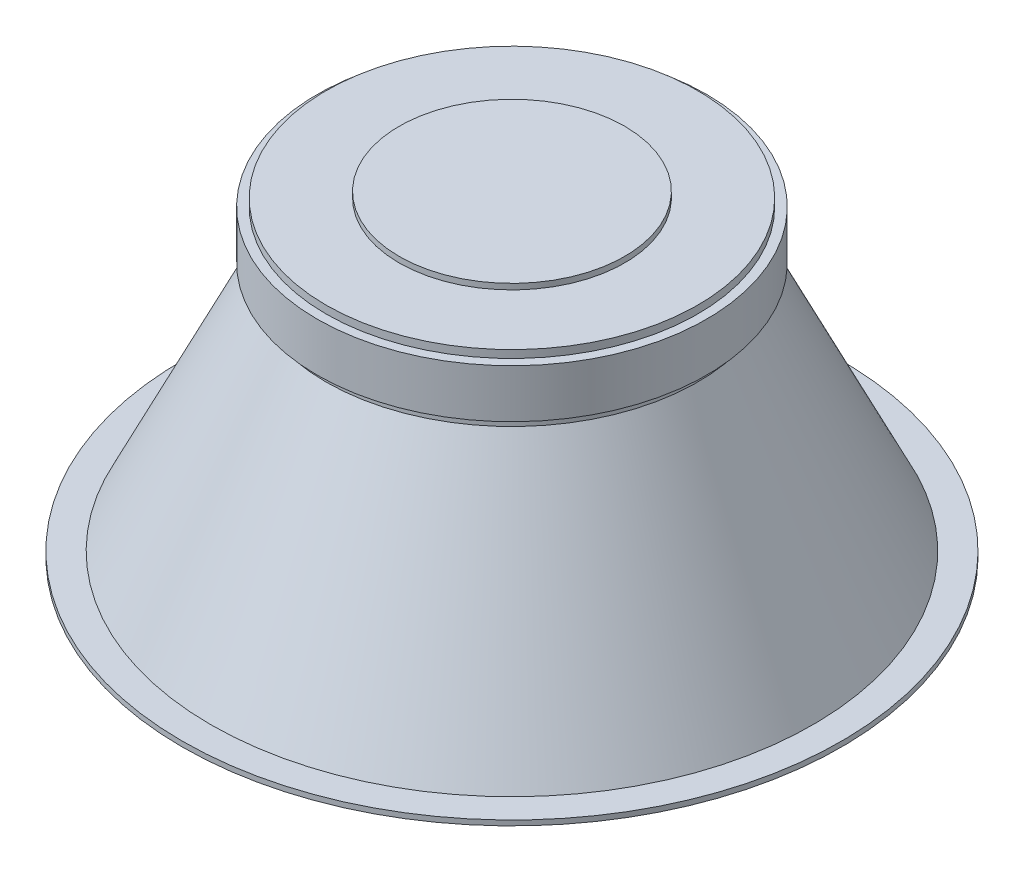
SolidWorks part; units mm, degrees
ref_plane "Front Plane" through (0, 0, 0) normal (0, 0, 1) x (1, 0, 0)
ref_plane "Top Plane" through (0, 0, 0) normal (0, 1, 0) x (1, 0, 0)
ref_plane "Right Plane" through (0, 0, 0) normal (1, 0, 0) x (0, 0, -1)
sketch "Sketch7" plane through (0, 0, 0) normal (1, 0, 0) x (0, 0, -1)
  line L0 (12.5742, 123.5) -> (-31.4258, 123.5)
  line L1 (-59.9258, 118.2794) -> (-63.3928, 118.2794)
  line L2 (-59.9258, 121.2831) -> (-59.9258, 118.2794)
  line L3 (-59.9258, 95.2831) -> (-104.9008, 2)
  line L4 (-104.9008, 2) -> (-116.0133, 2)
  line L5 (-59.9258, 99.3602) -> (-59.9258, 95.2831)
  line L6 (-116.0133, 2) -> (-116.0133, 0)
  line L7 (-116.0133, 0) -> (-102.3133, 0)
  line L8 (-63.3928, 99.3602) -> (-59.9258, 99.3602)
  line L9 (-102.3133, 0) -> (-102.3133, 2)
  line L25 (-91.7411, 3.4622) -> (-32.3943, 54.1395)
  line L26 (12.5742, 123.5) -> (12.5742, -9.999) construction
  line L27 (12.5742, 123.5) -> (12.5742, 39.6936)
  line L28 (-63.3928, 118.2794) -> (-63.3928, 99.3602)
  line L29 (-102.3133, 2) -> (-100.8367, 3.4622)
  line L30 (-96.2496, 2) -> (-94.773, 3.4622)
  line L31 (-93.2177, 2) -> (-91.7411, 3.4622)
  line L32 (-99.2815, 2) -> (-97.8048, 3.4622)
  line L33 (-100.8367, 3.4622) -> (-99.2815, 2)
  line L34 (-97.8048, 3.4622) -> (-96.2496, 2)
  line L35 (-94.773, 3.4622) -> (-93.2177, 2)
  line L36 (-31.4258, 123.5) -> (-31.4258, 121.2831)
  line L37 (-31.4258, 121.2831) -> (-59.9258, 121.2831)
  arc A0 (-32.3943, 54.1395) -> (12.5742, 39.6936) centre (12.5652, 116.8796) ccw
  point P2 (-116.0133, 1)
  point P3 (-77.5171, -3.2704)
  point P22 (0, 0)
  point P23 (0, 0)
  point P24 (0, 0)
  point P25 (0, 0)
  point P26 (-91.412, 3.6055)
  point P27 (0, 0)
  point P28 (0, 0)
  point P29 (0, 0)
  point P30 (0, 0)
  point P31 (10.3633, 139.7853)
  point P32 (0, 0)
  point P33 (10.3633, 139.7853)
  point P36 (0, 0)
  point P38 (10.3633, 139.7853)
  point P39 (0, 0)
  point P40 (0, 0)
  point P41 (0, 0)
  point P42 (0, 0)
  point P43 (0, 0)
  point P44 (-32.2085, 54.1395)
  point P45 (0, 0)
  point P46 (0, 0)
  point P47 (0, 0)
  point P48 (12.76, 39.6936)
  point P49 (-73.8282, 180.2422)
  point P52 (0, 0)
  point P53 (0, 0)
  point P54 (0, 0)
  point P55 (0, 0)
  point P56 (0, 0)
  point P57 (0, 0)
  point P58 (0, 0)
  point P59 (0, 0)
  point P60 (0, 0)
  point P61 (0, 0)
  point P62 (-31.24, 124.9533)
  dimension "D1" = 128.5875
  dimension "D2" = 117.475
  dimension "D3" = 13.7
  dimension "D5" = 26
  dimension "D6" = 44
  dimension "D7" = 123.5
  dimension "D4" = 72.5
revolve "Revolve1" add sketch "Sketch7" angle 360 about L26
equation "\"LENGTH\" = 1000mm"
equation "\"WIDTH\" = 300mm"
equation "\"HEIGHT\" = 300mm"
equation "\"HOUSING_DEPTH\" = 4mm"
equation "\"PLY\"= 12mm"
equation "\"CENTER_BRACE_LENGTH\" = 393mm"
equation "\"PANEL_WIDTH\"= \"LENGTH\" - \"CENTER_BRACE_LENGTH\" * 2 - \"PLY\" * 4"
equation "\"PANEL_SMALL_HEIGHT\" = 70mm"
equation "\"PORT_WIDTH\" = 90mm"
equation "\"PORT_RADIUS\" = 15mm"
equation "\"PORT_BRACE_HEIGHT\" = 92mm"
equation "\"DOWEL_SIZE\" = 0.25in"
equation "\"DOWEL_OFFSET\" = 30mm"
equation "\"GW1058_outside_diameter\" = 10.125in"
equation "\"GW1058_baffle_cutout_diameter\" = 9.25in"
equation "\"D1@Sketch7\"=\"GW1058_outside_diameter\" / 2"
equation "\"D2@Sketch7\"=\"GW1058_baffle_cutout_diameter\" / 2"
equation "\"D6@Sketch7\"=88/2mm"
